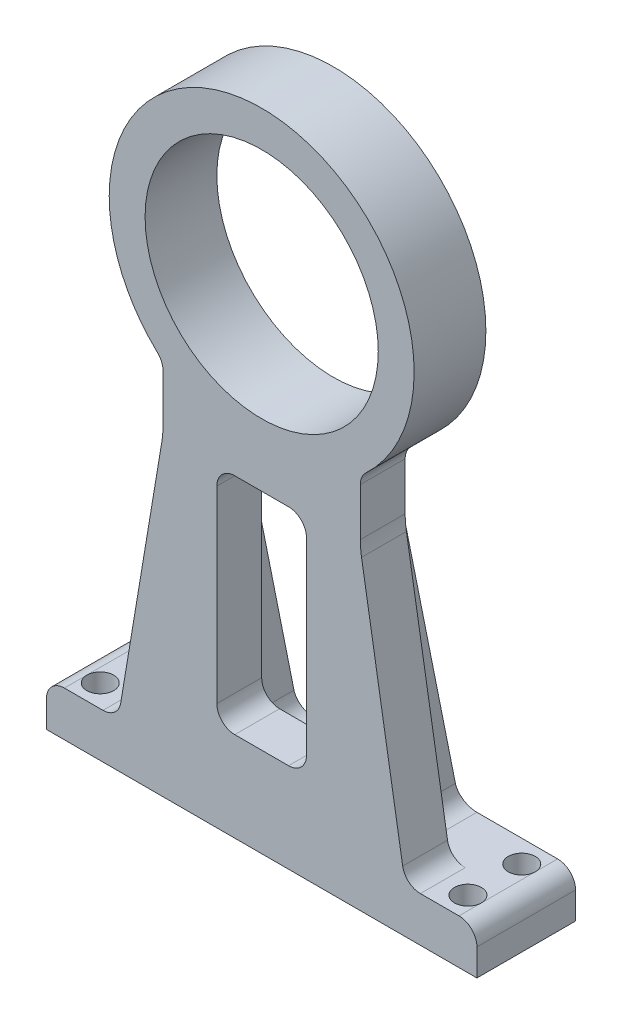
SolidWorks part; units mm, degrees
material "6061-T6 (SS)"
ref_plane "前视基准面" through (0, 0, 0) normal (0, 0, 1) x (1, 0, 0)
ref_plane "上视基准面" through (0, 0, 0) normal (0, 1, 0) x (1, 0, 0)
ref_plane "右视基准面" through (0, 0, 0) normal (1, 0, 0) x (0, 0, -1)
sketch "草图1" plane through (0, 0, 0) normal (0, 0, 1) x (1, 0, 0)
  line L0 (0, 37.4312) -> (0, -62.599) construction
  line L1 (-24, -55) -> (24, -55)
  line L2 (24, -55) -> (24, -50)
  line L3 (24, -50) -> (16, -50)
  line L4 (11, -20) -> (11, -12.9615)
  line L5 (-24, -55) -> (-24, -50)
  line L6 (-11, -20) -> (-11, -12.9615)
  line L7 (-24, -50) -> (-16, -50)
  line L8 (-16, -50) -> (-11, -20)
  line L9 (-5, -20) -> (5, -20)
  line L10 (-5, -20) -> (-5, -45)
  line L11 (-5, -45) -> (5, -45)
  line L12 (5, -20) -> (5, -45)
  line L13 (-5, -20) -> (5, -45) construction
  line L14 (-5, -45) -> (5, -20) construction
  line L15 (16, -50) -> (11, -20)
  circle A0 centre (0, 0) radius 13
  arc A1 (11, -12.9615) -> (-11, -12.9615) centre (0, 0) ccw
  point P3 (0, -32.5)
  point P15 (0, -55)
  dimension "D1" = 26
  dimension "D2" = 34
  dimension "D3" = 5
  dimension "D4" = 22
  dimension "D5" = 55
  dimension "D6" = 48
  dimension "D7" = 10
  dimension "D8" = 25
  dimension "D9" = 8
  dimension "D10" = 30
  dimension "D11" = 6
extrude "凸台-拉伸1" add sketch "草图1" along normal mid plane 5
sketch "草图2" plane through (0, -55, 0) normal (0, -1, 0) x (1, 0, 0)
  line L0 (-27.8992, 0) -> (28.6856, 0) construction
  line L1 (0, 22.1473) -> (0, -17.8656) construction
  line L2 (-24, 2.5) -> (-24, -2.5) construction
  point P5 (-20.5, 0)
  point P8 (20.5, 0)
  dimension "D1" = 3.5
sketch "草图8" plane through (0, 0, 0) normal (0, 0, 1) x (1, 0, 0)
  line L0 (-24, -50) -> (-24, -55) construction
  line L1 (-24, -50) -> (-24, -55)
  line L2 (24, -55) -> (24, -50) construction
  line L3 (24, -55) -> (24, -50)
  line L4 (-24, -55) -> (24, -55) construction
  line L5 (-24, -55) -> (24, -55)
  line L6 (-24, -50) -> (24, -50)
extrude "凸台-拉伸2" add sketch "草图8" along normal blind 2.5 and the other way blind 8.5
sketch "草图9" plane through (0, -55, 0) normal (0, -1, 0) x (1, 0, 0)
  line L0 (-30.485, -3) -> (33.3441, -3) construction
  line L1 (0, 21.6197) -> (0, -17.532) construction
  line L3 (-24, 2.5) -> (-24, -8.5) construction
  circle A0 centre (-20.5, 0) radius 1.5
  circle A1 centre (20.5, 0) radius 1.5
  circle A2 centre (-20.5, -6) radius 1.5
  circle A3 centre (20.5, -6) radius 1.5
  point P18 (-24, -3)
  dimension "D1" = 3
  dimension "D2" = 6
  dimension "D3" = 41
extrude "切除-拉伸1" cut sketch "草图9" against normal up to next
sketch "草图11" plane through (-11, 0, 0) normal (-1, 0, 0) x (0, 0, 1)
  line L0 (-2.5, -20) -> (-8.5, -50)
  line L1 (2.5, -50) -> (-8.5, -50) construction
  line L2 (2.5, -50) -> (-8.5, -50) construction
rib "筋3" sketch "草图11" sketch "草图11" thickness 4 extrusion direction parallel to sketch draft on no parameters "D1"=4
mirror "镜向1" about plane through (0, 0, 0) normal (1, 0, 0) of "筋3"
fillet "圆角1" radius 2 12 edges at (-5, -20, 0) (5, -20, 0) (5, -45, 0) (-5, -45, 0) (24, -50, -3) (-24, -50, -3) (-16, -50, 0) (16, -50, 0) (-11, -50, -5.5) (-7, -50, -5.5) (7, -50, -5.5) (11, -50, -5.5)
fillet "圆角2" radius 2 2 edges at (-11, -12.9615, 0) (11, -12.9615, 0)
fillet "圆角3" radius 10 2 edges at (11, -20, 0) (-11, -20, 0)
sketch "草图12" plane through (0, 0, -2.5) normal (0, 0, -1) x (-1, 0, 0)
  circle A0 centre (0, 0) radius 17
  circle A1 centre (0, 0) radius 13 construction
  circle A2 centre (0, 0) radius 13
  arc A3 (11.6316, -12.3978) -> (-11.6316, -12.3978) centre (0, 0) ccw construction
extrude "凸台-拉伸3" add sketch "草图12" along normal blind 3
move or copy body "实体-移动/复制1" [suppressed] bodies to move or copy 107
